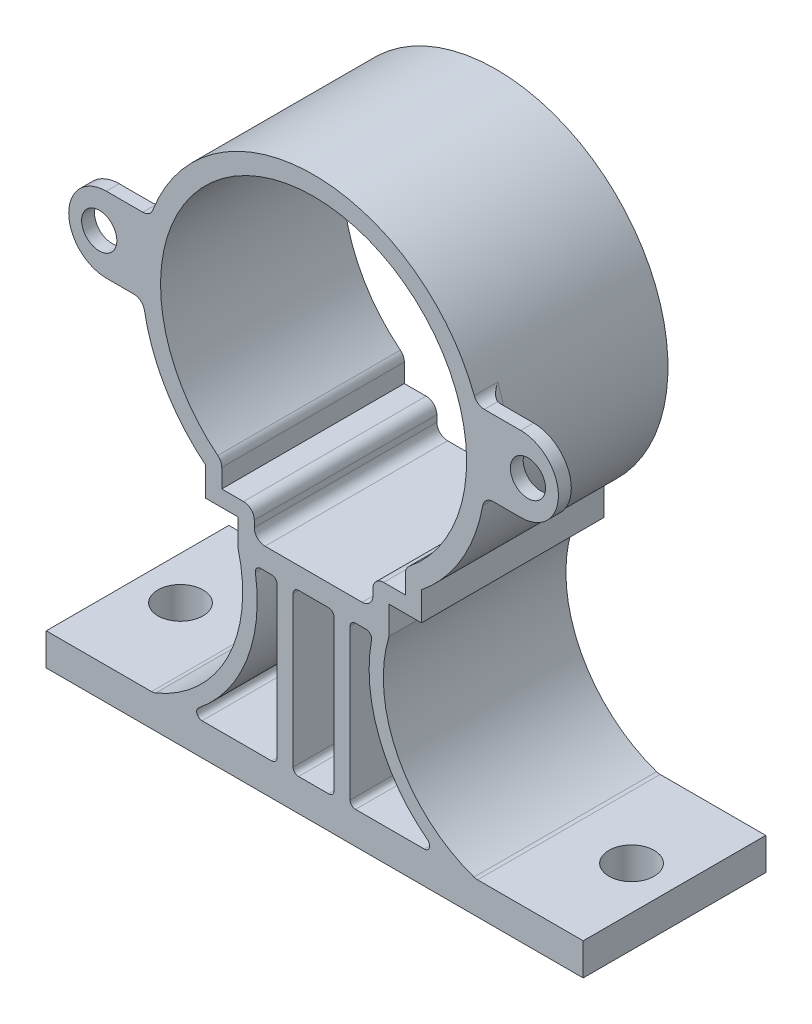
SolidWorks part; units mm, degrees
material "PLA"
ref_plane "Alzado" through (0, 0, 0) normal (0, 0, 1) x (1, 0, 0)
ref_plane "Planta" through (0, 0, 0) normal (0, 1, 0) x (1, 0, 0)
ref_plane "Vista lateral" through (0, 0, 0) normal (1, 0, 0) x (0, 0, -1)
sketch "Croquis1" plane through (0, 0, 0) normal (0, 0, 1) x (1, 0, 0)
  line L0 (8.55, 13.6076) -> (8.55, 11.8771)
  line L1 (8.55, 11.8771) -> (6.52, 11.8771)
  line L2 (5.52, 10.8771) -> (5.52, 10.2771)
  line L3 (4.52, 9.2771) -> (-4.52, 9.2771)
  line L4 (-5.52, 10.2771) -> (-5.52, 10.8771)
  line L5 (-6.52, 11.8771) -> (-8.55, 11.8771)
  line L6 (-8.55, 11.8771) -> (-8.55, 13.6076)
  line L7 (-10.05, 10.3771) -> (-7.02, 10.3771)
  line L8 (-7.02, 10.3771) -> (-7.02, 7.7771)
  line L9 (-7.02, 7.7771) -> (7.02, 7.7771)
  line L10 (7.02, 7.7771) -> (7.02, 10.3771)
  line L11 (7.02, 10.3771) -> (10.05, 10.3771)
  line L12 (-10.05, 10.3771) -> (-10.05, 13.0473)
  line L13 (10.05, 10.3771) -> (10.05, 13.0473)
  arc A0 (8.9238, 14.3873) -> (-8.9238, 14.3873) centre (0, 25.4971) ccw
  circle A1 centre (0, 11.2471) radius 7.98 construction
  arc A3 (5.52, 10.2771) -> (4.52, 9.2771) centre (4.52, 10.2771) cw
  arc A4 (10.05, 13.0473) -> (-10.05, 13.0473) centre (0, 25.4971) ccw
  arc A5 (-4.52, 9.2771) -> (-5.52, 10.2771) centre (-4.52, 10.2771) cw
  arc A6 (8.55, 13.6076) -> (8.9238, 14.3873) centre (9.55, 13.6076) cw
  arc A7 (6.52, 11.8771) -> (5.52, 10.8771) centre (6.52, 10.8771) ccw
  arc A8 (-5.52, 10.8771) -> (-6.52, 11.8771) centre (-6.52, 10.8771) ccw
  arc A9 (-8.55, 13.6076) -> (-8.9238, 14.3873) centre (-9.55, 13.6076) ccw
  point P17 (0, 9.2771)
  point P20 (-10.05, 11.7122)
  point P24 (-5.52, 10.5771)
  point P25 (0, 39.7471)
  point P26 (0, 40.7324)
  point P27 (5.52, 9.2771)
  point P30 (-5.52, 9.2771)
  point P33 (8.55, 14.0971)
  point P36 (5.52, 11.8771)
  point P39 (-5.52, 11.8771)
  point P42 (-8.55, 14.0971)
  dimension "D1" = 28.5
  dimension "D2" = 15.96
  dimension "D5" = 16.22
  dimension "D7" = 16
  dimension "D14" = 1
  dimension "D3" = 17.1
  dimension "D4" = 11.04
  dimension "D6" = 2.6
  dimension "D8" = 1.5
  dimension "D9" = 1.5
  dimension "D10" = 1.5
  dimension "D11" = 1.5
  dimension "D12" = 1.5
  dimension "D13" = 1.5
extrude "Saliente-Extruir1" add sketch "Croquis1" against normal blind 17
sketch "Croquis2" plane through (0, 0, 0) normal (0, 0, 1) x (1, 0, 0)
  circle A0 centre (0, 11.2471) radius 7.98 construction
  circle A1 centre (0, 11.2471) radius 7.98
  circle A2 centre (0, 11.2471) radius 9.48
  dimension "D1" = 18.96
extrude "Saliente-Extruir2" add sketch "Croquis2" along normal blind 5 and the other way blind 0.5
sketch "Croquis3" plane through (0, 0, 5) normal (0, 0, 1) x (1, 0, 0)
  line L0 (-15.5, -10.7329) -> (15.5, -10.7329)
  line L3 (-7.02, 7.7771) -> (-7.02, 8.0949)
  line L4 (-7.02, 10.3771) -> (-7.02, 7.7771) construction
  line L5 (-7.02, 8.0949) -> (7.02, 8.0949)
  line L6 (7.02, 7.7771) -> (7.02, 10.3771) construction
  line L7 (7.02, 8.0949) -> (7.02, 7.7771)
  line L9 (-11.9402, -7.7329) -> (-3.9021, -7.7329)
  line L12 (-5.52, 7.2771) -> (-3.9021, 7.2771)
  line L13 (-7.02, 7.7771) -> (7.02, 7.7771) construction
  line L14 (-3.4021, 6.7771) -> (-3.4021, -7.2329)
  line L15 (3.4021, 6.7771) -> (3.4021, -7.2329)
  line L16 (1.9021, 6.7771) -> (1.9021, -7.2329)
  line L17 (-1.9021, 6.7771) -> (-1.9021, -7.2329)
  line L18 (-1.4021, 7.2771) -> (1.4021, 7.2771)
  line L19 (3.9021, 7.2771) -> (5.52, 7.2771)
  line L20 (3.9021, -7.7329) -> (11.9402, -7.7329)
  line L21 (-1.4021, -7.7329) -> (1.4021, -7.7329)
  line L22 (15.1063, -7.7329) -> (25.1063, -7.7329)
  line L23 (25.1063, -7.7329) -> (25.1063, -10.7329)
  line L24 (25.1063, -10.7329) -> (15.5, -10.7329)
  line L25 (-14.8937, -7.7329) -> (-24.8937, -7.7329)
  line L26 (-24.8937, -7.7329) -> (-24.8937, -10.7329)
  line L27 (-24.8937, -10.7329) -> (-15.5, -10.7329)
  circle A2 centre (0, 11.2471) radius 7.98 construction
  arc A3 (10.05, 13.0473) -> (-10.05, 13.0473) centre (0, 25.4971) ccw construction
  arc A6 (-3.4021, -7.2329) -> (-3.9021, -7.7329) centre (-3.9021, -7.2329) cw
  arc A7 (-1.9021, -7.2329) -> (-1.4021, -7.7329) centre (-1.4021, -7.2329) ccw
  arc A8 (1.9021, -7.2329) -> (1.4021, -7.7329) centre (1.4021, -7.2329) cw
  arc A9 (3.4021, -7.2329) -> (3.9021, -7.7329) centre (3.9021, -7.2329) ccw
  arc A10 (3.4021, 6.7771) -> (3.9021, 7.2771) centre (3.9021, 6.7771) cw
  arc A11 (1.9021, 6.7771) -> (1.4021, 7.2771) centre (1.4021, 6.7771) ccw
  arc A12 (-1.9021, 6.7771) -> (-1.4021, 7.2771) centre (-1.4021, 6.7771) cw
  arc A13 (-3.4021, 6.7771) -> (-3.9021, 7.2771) centre (-3.9021, 6.7771) ccw
  arc A14 (-14.8937, -7.7329) -> (-7.02, 7.7771) centre (-19.7457, 4.4838) ccw
  arc A16 (-11.9402, -7.7329) -> (-5.52, 7.2771) centre (-19.7457, 4.4838) ccw
  arc A17 (7.02, 7.7771) -> (15.1063, -7.7329) centre (19.0508, 4.1866) ccw
  arc A18 (5.52, 7.2771) -> (11.9402, -7.7329) centre (19.0508, 4.1866) ccw
  point P10 (0, -10.7329)
  point P29 (15.5, 21.5285)
  point P49 (-1.9021, -7.7329)
  point P54 (3.4021, -7.7329)
  point P57 (3.4021, 7.2771)
  point P60 (1.9021, 7.2771)
  point P63 (-1.9021, 7.2771)
  point P69 (0, 8.0949)
  point P71 (0, -7.7329)
  dimension "D9" = 0.5
  dimension "D2" = 21.98
  dimension "D3" = 3
  dimension "D5" = 50
  dimension "D6" = 0.5
  dimension "D7" = 1.5
  dimension "D8" = 1.5
  dimension "D10" = 10
  dimension "D11" = 10
  dimension "D12" = 1.5
  dimension "D13" = 1.5
extrude "Saliente-Extruir3" add sketch "Croquis3" against normal blind 17 from surface starting at face at (0, 18.7818, 0)
sketch "Croquis4" plane through (0, 0, 0) normal (0, 0, 1) x (1, 0, 0)
  line L0 (19.29, 30.5171) -> (14.6643, 30.5171)
  line L1 (19.29, 23.4971) -> (15.1701, 23.4971)
  line L2 (15.1701, 23.4971) -> (14.6643, 30.5171)
  line L3 (0, 0) -> (0, 13.0903) construction
  line L7 (-15.1701, 23.4971) -> (-14.6643, 30.5171)
  line L8 (-19.29, 23.4971) -> (-15.1701, 23.4971)
  line L9 (-19.29, 30.5171) -> (-14.6643, 30.5171)
  circle A0 centre (-19.96, 27.0071) radius 1.64
  arc A1 (19.29, 23.4971) -> (19.29, 30.5171) centre (19.29, 27.0071) ccw
  arc A2 (10.05, 13.0473) -> (-10.05, 13.0473) centre (0, 25.4971) ccw construction
  circle A3 centre (19.96, 27.0071) radius 1.64
  arc A6 (-19.29, 23.4971) -> (-19.29, 30.5171) centre (-19.29, 27.0071) cw
  point P3 (0, 41.4971)
  point P4 (16, 25.4971)
  point P10 (22.8, 27.0071)
  point P13 (21.6, 27.0071)
  point P25 (-21.6, 27.0071)
  point P26 (-16, 25.4971)
  dimension "D4" = 3.28
  dimension "D1" = 7.02
  dimension "D2" = 18
  dimension "D3" = 6.8
  dimension "D5" = 1.2
extrude "Saliente-Extruir4" add sketch "Croquis4" against normal blind 1.2
sketch "Croquis8" plane through (0, 0, 5) normal (0, 0, 1) x (1, 0, 0)
  circle A0 centre (0, 11.2471) radius 7.98
  circle A1 centre (0, 11.2471) radius 9.48
extrude "Cortar-Extruir1" cut sketch "Croquis8" against normal up to surface (5 mm away) up to face at (0, 21.732, 0)
sketch "Croquis9" plane through (0, 0, 0) normal (0, 0, 1) x (1, 0, 0)
  line L3 (3.4021, 6.7771) -> (3.4021, -7.2329)
  line L4 (1.9021, -7.2329) -> (1.9021, 6.7771)
  line L5 (-1.4021, -7.7329) -> (1.4021, -7.7329)
  line L6 (-1.9021, 6.7771) -> (-1.9021, -7.2329)
  line L7 (1.4021, 7.2771) -> (-1.4021, 7.2771)
  line L8 (1.9021, 1.9599) -> (1.9021, 3.4971)
  line L9 (-1.4021, -7.7329) -> (1.4021, -7.7329)
  line L10 (-1.9021, 3.4971) -> (-1.9021, 1.9599)
  line L12 (3.9021, -7.7329) -> (11.9402, -7.7329)
  line L13 (5.52, 7.2771) -> (3.9021, 7.2771)
  line L14 (3.4021, 4.0287) -> (3.4021, 2.3986)
  line L17 (-3.9021, 7.2771) -> (-5.52, 7.2771)
  line L18 (-11.9402, -7.7329) -> (-3.9021, -7.7329)
  line L19 (-3.4021, -7.2329) -> (-3.4021, 6.7771)
  line L22 (-3.4021, 2.3986) -> (-3.4021, 4.0287)
  line L24 (25.1063, -7.7329) -> (15.1063, -7.7329)
  line L25 (7.02, 7.7771) -> (7.02, 8.0949)
  line L26 (7.02, 8.0949) -> (-7.02, 8.0949)
  line L27 (-7.02, 8.0949) -> (-7.02, 7.7771)
  line L28 (-14.8937, -7.7329) -> (-24.8937, -7.7329)
  line L29 (-24.8937, -7.7329) -> (-24.8937, -10.7329)
  line L30 (-24.8937, -10.7329) -> (-15.5, -10.7329)
  line L31 (-15.5, -10.7329) -> (15.5, -10.7329)
  line L32 (15.5, -10.7329) -> (25.1063, -10.7329)
  line L33 (25.1063, -10.7329) -> (25.1063, -7.7329)
  line L43 (25.1063, -10.7329) -> (25.1063, -7.7329)
  line L47 (7.02, 7.7771) -> (7.02, 10.3771)
  line L48 (7.02, 10.3771) -> (10.05, 10.3771)
  line L49 (10.05, 10.3771) -> (10.05, 13.0473)
  line L50 (-10.05, 13.0473) -> (-10.05, 10.3771)
  line L51 (-10.05, 10.3771) -> (-7.02, 10.3771)
  line L52 (-7.02, 10.3771) -> (-7.02, 7.7771)
  line L53 (-7.02, 7.7771) -> (7.02, 7.7771)
  line L55 (7.9324, 10.3771) -> (9.44, 10.3771)
  line L58 (-9.44, 10.3771) -> (-7.9324, 10.3771)
  line L61 (6.52, 11.8771) -> (8.55, 11.8771)
  line L62 (8.55, 11.8771) -> (8.55, 13.6076)
  line L63 (-8.55, 13.6076) -> (-8.55, 11.8771)
  line L64 (-8.55, 11.8771) -> (-6.52, 11.8771)
  line L65 (-5.52, 10.8771) -> (-5.52, 10.2771)
  line L66 (-4.52, 9.2771) -> (4.52, 9.2771)
  line L67 (5.52, 10.2771) -> (5.52, 10.8771)
  line L68 (7.9551, 11.8771) -> (8.55, 11.8771)
  line L69 (8.55, 11.8771) -> (8.55, 13.6076)
  line L70 (-8.55, 13.6076) -> (-8.55, 11.8771)
  line L71 (-8.55, 11.8771) -> (-7.9551, 11.8771)
  arc A0 (-7.9324, 10.3771) -> (-6.8883, 7.2183) centre (0, 11.2471) ccw
  arc A1 (-9.44, 10.3771) -> (-6.6008, 4.4428) centre (0, 11.2471) ccw
  arc A2 (-8.9402, 14.4005) -> (-8.9238, 14.3873) centre (0, 25.4971) ccw
  arc A3 (10.05, 13.0473) -> (-10.05, 13.0473) centre (0, 25.4971) ccw
  arc A4 (7.02, 7.7771) -> (15.1063, -7.7329) centre (19.0508, 4.1866) ccw
  arc A5 (3.4021, -7.2329) -> (3.9021, -7.7329) centre (3.9021, -7.2329) ccw
  arc A6 (1.4021, -7.7329) -> (1.9021, -7.2329) centre (1.4021, -7.2329) ccw
  arc A7 (-1.9021, -7.2329) -> (-1.4021, -7.7329) centre (-1.4021, -7.2329) ccw
  arc A8 (-1.4021, 7.2771) -> (-1.9021, 6.7771) centre (-1.4021, 6.7771) ccw
  arc A9 (1.9021, 6.7771) -> (1.4021, 7.2771) centre (1.4021, 6.7771) ccw
  arc A10 (1.4021, -7.7329) -> (1.9021, -7.2329) centre (1.4021, -7.2329) ccw
  arc A11 (-1.9021, -7.2329) -> (-1.4021, -7.7329) centre (-1.4021, -7.2329) ccw
  arc A14 (5.52, 7.2771) -> (11.9402, -7.7329) centre (19.0508, 4.1866) ccw
  arc A15 (3.9021, 7.2771) -> (3.4021, 6.7771) centre (3.9021, 6.7771) ccw
  arc A17 (5.2087, 5.2015) -> (5.1986, 3.3197) centre (19.0508, 4.1866) ccw
  arc A19 (-14.8937, -7.7329) -> (-7.02, 7.7771) centre (-19.7457, 4.4838) ccw
  arc A20 (6.8521, 7.1569) -> (6.4966, 4.3432) centre (19.0508, 4.1866) ccw
  arc A21 (-6.6008, 4.4428) -> (-6.8883, 7.2183) centre (-19.7457, 4.4838) ccw
  arc A23 (-11.9402, -7.7329) -> (-5.52, 7.2771) centre (-19.7457, 4.4838) ccw
  arc A24 (-3.9021, -7.7329) -> (-3.4021, -7.2329) centre (-3.9021, -7.2329) ccw
  arc A25 (-3.4021, 6.7771) -> (-3.9021, 7.2771) centre (-3.9021, 6.7771) ccw
  arc A26 (-5.2904, 3.3806) -> (-5.2688, 5.2538) centre (-19.7457, 4.4838) ccw
  arc A27 (-3.9021, -7.7329) -> (-3.4021, -7.2329) centre (-3.9021, -7.2329) ccw
  arc A29 (-5.2688, 5.2538) -> (-3.4021, 4.0287) centre (0, 11.2471) ccw
  arc A30 (-5.2904, 3.3806) -> (-3.4021, 2.3986) centre (0, 11.2471) ccw
  arc A31 (-1.9021, 3.4971) -> (1.9021, 3.4971) centre (0, 11.2471) ccw
  arc A32 (-1.9021, 1.9599) -> (1.9021, 1.9599) centre (0, 11.2471) ccw
  arc A33 (3.4021, 4.0287) -> (5.2087, 5.2015) centre (0, 11.2471) ccw
  arc A34 (3.4021, 2.3986) -> (5.1986, 3.3197) centre (0, 11.2471) ccw
  arc A35 (8.9238, 14.3873) -> (8.55, 13.6076) centre (9.55, 13.6076) ccw
  arc A36 (8.9238, 14.3873) -> (-8.9238, 14.3873) centre (0, 25.4971) ccw
  arc A37 (-8.55, 13.6076) -> (-8.9238, 14.3873) centre (-9.55, 13.6076) ccw
  arc A38 (-5.52, 10.8771) -> (-6.52, 11.8771) centre (-6.52, 10.8771) ccw
  arc A39 (-5.52, 10.2771) -> (-4.52, 9.2771) centre (-4.52, 10.2771) ccw
  arc A40 (4.52, 9.2771) -> (5.52, 10.2771) centre (4.52, 10.2771) ccw
  arc A41 (6.52, 11.8771) -> (5.52, 10.8771) centre (6.52, 10.8771) ccw
  arc A42 (8.9238, 14.3873) -> (8.55, 13.6076) centre (9.55, 13.6076) ccw
  arc A43 (8.9238, 14.3873) -> (8.9402, 14.4005) centre (0, 25.4971) ccw
  arc A44 (-8.55, 13.6076) -> (-8.9238, 14.3873) centre (-9.55, 13.6076) ccw
  arc A45 (6.8521, 7.1569) -> (7.9324, 10.3771) centre (0, 11.2471) ccw
  arc A46 (6.4966, 4.3432) -> (9.44, 10.3771) centre (0, 11.2471) ccw
  arc A47 (-7.9324, 10.3771) -> (-6.8883, 7.2183) centre (0, 11.2471) ccw
  arc A48 (-9.44, 10.3771) -> (-6.6008, 4.4428) centre (0, 11.2471) ccw
  arc A49 (7.9551, 11.8771) -> (-7.9551, 11.8771) centre (0, 11.2471) ccw
  arc A50 (8.9402, 14.4005) -> (-8.9402, 14.4005) centre (0, 11.2471) ccw
  arc A51 (-5.2688, 5.2538) -> (-3.4021, 4.0287) centre (0, 11.2471) ccw
  arc A52 (-5.2904, 3.3806) -> (-3.4021, 2.3986) centre (0, 11.2471) ccw
  arc A53 (-1.9021, 3.4971) -> (1.9021, 3.4971) centre (0, 11.2471) ccw
  arc A54 (-1.9021, 1.9599) -> (1.9021, 1.9599) centre (0, 11.2471) ccw
  arc A55 (3.4021, 4.0287) -> (5.2087, 5.2015) centre (0, 11.2471) ccw
  arc A56 (3.4021, 2.3986) -> (5.1986, 3.3197) centre (0, 11.2471) ccw
  arc A57 (6.8521, 7.1569) -> (7.9324, 10.3771) centre (0, 11.2471) ccw
  arc A58 (6.4966, 4.3432) -> (9.44, 10.3771) centre (0, 11.2471) ccw
  dimension "D1" = 0
  dimension "D2" = 0
  dimension "D3" = 0
  dimension "D4" = 0
  dimension "D5" = 0
  dimension "D6" = 0
extrude "Cortar-Extruir2" cut sketch "Croquis9" against normal through all contours A43 A50 A2 A44 L70 L71 A49 L68 L69 A42 | A20 A46 L55 A45 | L14 A34 A17 A33 | L10 A32 L8 A31 | A26 A30 L22 A29 | A1 A21 A0 L58 region at (4.3124, 3.6935, 0) region at (0, 2.5877, 0) region at (-4.3533, 3.7167, 0) region at (7.9356, 7.7842, 0) region at (-7.9665, 7.838, 0) region at (0, 19.4266, 0)
fillet "Redondeo1" radius 1 8 edges at (15.8745, 23.4971, -0.6) (15.9249, 27.0452, -1.2) (15.1921, 30.5171, -0.6) (-15.8745, 23.4971, -0.6) (-15.9249, 27.0452, -1.2) (-15.1921, 30.5171, -0.6) (15.1063, -7.7329, -8.5) (-14.8937, -7.7329, -8.5)
fillet "Redondeo2" radius 0.5 4 edges at (-11.9402, -7.7329, -8.5) (11.9402, -7.7329, -8.5) (5.52, 7.2771, -8.5) (-5.52, 7.2771, -8.5)
sketch "Croquis11" plane through (0, -7.7329, 0) normal (0, 1, 0) x (1, 0, 0)
  line L0 (-24.8937, 17) -> (-24.8937, 0) construction
  line L1 (25.1063, 17) -> (25.1063, 0) construction
  circle A0 centre (-20.8937, 8.5) radius 2.1
  circle A1 centre (21.1063, 8.5) radius 2.1
  dimension "D1" = 4.2
  dimension "D2" = 4
  dimension "D3" = 4
extrude "Cortar-Extruir3" cut sketch "Croquis11" against normal through all
